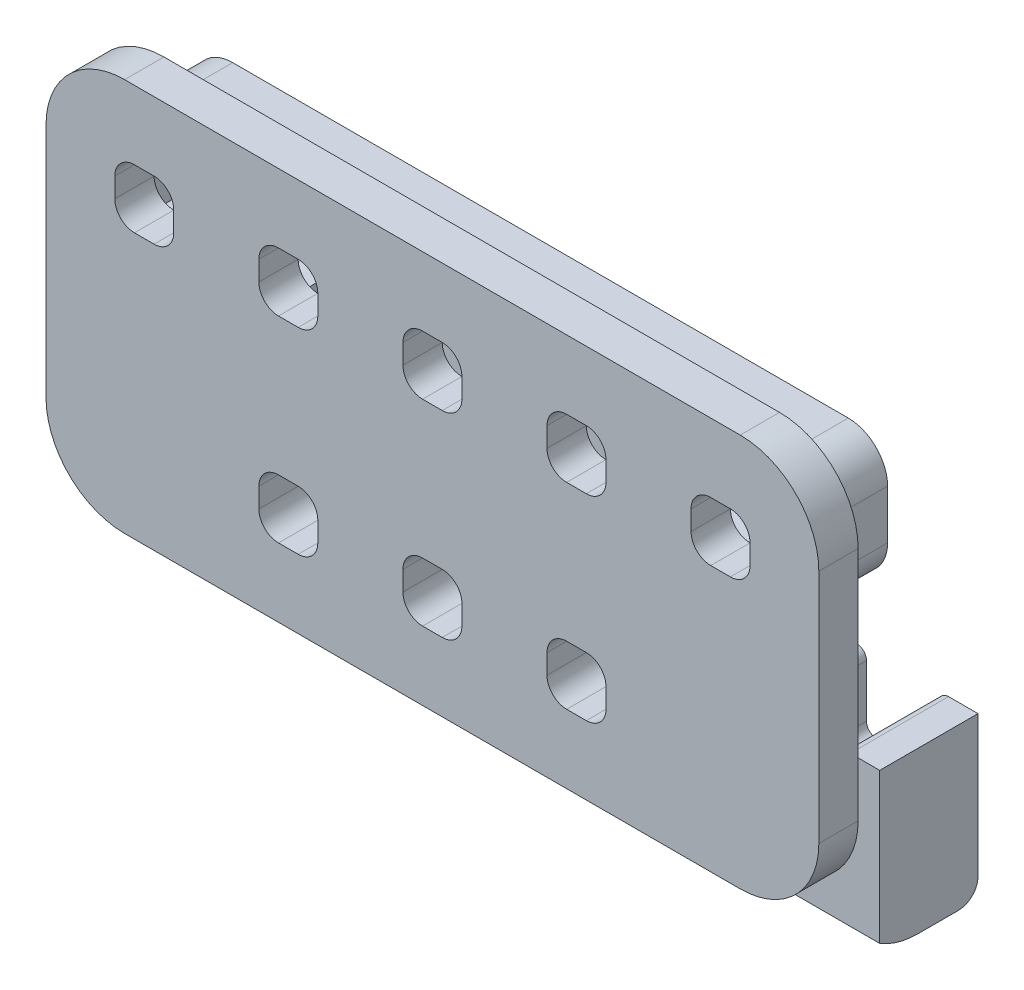
SolidWorks part; units mm, degrees
ref_plane "Front Plane" through (0, 0, 0) normal (0, 0, 1) x (1, 0, 0)
ref_plane "Top Plane" through (0, 0, 0) normal (0, 1, 0) x (1, 0, 0)
ref_plane "Right Plane" through (0, 0, 0) normal (1, 0, 0) x (0, 0, -1)
sketch "Sketch1" plane through (0, 0, 0) normal (0, 0, 1) x (1, 0, 0)
  line L0 (-3.675, 0) -> (-3.675, 7.35) construction
  line L1 (0, 0) -> (-7.35, 0)
  line L2 (0, 0) -> (0, 7.35)
  line L3 (0, 7.35) -> (-7.35, 7.35) construction
  line L4 (-7.35, 0) -> (-7.35, 7.35)
  line L5 (0, 7.35) -> (4, 7.35)
  line L6 (4, 7.35) -> (4, -9)
  line L7 (4, -9) -> (-11.35, -9)
  line L8 (-3.675, -9) -> (-3.675, 0) construction
  line L9 (-11.35, 7.35) -> (-11.35, -9)
  line L10 (-7.35, 7.35) -> (-11.35, 7.35)
  arc A0 (-11.35, -2.7355) -> (4, -2.7355) centre (-3.675, 3.675) ccw
  arc A1 (4, -2.7355) -> (-11.35, -2.7355) centre (-3.675, 3.675) ccw construction
  arc A2 (4, -6.4121) -> (-11.35, -6.4121) centre (-3.675, 3.675) ccw
  arc A3 (-3.675, -9) -> (4, -6.4121) centre (-3.675, 3.675) ccw construction
  arc A4 (-11.35, -6.4121) -> (-3.675, -9) centre (-3.675, 3.675) ccw construction
  point P14 (0, 0)
  dimension "D2" = 20
  dimension "D1" = 7.35
  dimension "D3" = 9
  dimension "D4" = 4
extrude "Boss-Extrude1" add sketch "Sketch1" along normal blind 10 contours L7 L9 L10 L4 L1 L2 L5 L6
sketch "Sketch2" plane through (4, 0, 0) normal (1, 0, 0) x (0, 0, -1)
  line L0 (0, 7.35) -> (0, -9) construction
  line L1 (-10, -9) -> (0, -9)
  line L2 (-10, -9) -> (-10, -3)
  line L3 (-10, -3) -> (0, -3)
  line L4 (0, -9) -> (0, -3)
  dimension "D1" = 6
extrude "Boss-Extrude2" add sketch "Sketch2" along normal blind 23.975
sketch "Sketch3" plane through (0, 0, 10) normal (0, 0, 1) x (1, 0, 0)
  line L0 (27.975, -3) -> (27.975, -9) construction
  line L1 (4, -9) -> (27.975, -9)
  line L2 (4, -9) -> (4, 5.85)
  line L3 (4, 5.85) -> (27.975, 5.85)
  line L4 (27.975, -9) -> (27.975, 5.85)
  line L5 (0, 7.35) -> (4, 7.35) construction
  line L6 (-3.675, 0) -> (-3.675, 7.35) construction
  circle A0 centre (-3.675, 3.675) radius 10
  line M3 (4, -3) -> (4, 7.35)
  line M10 (-11.35, -9) -> (27.975, -9)
  line M11 (27.975, -9) -> (27.975, -3)
  line M12 (27.975, -3) -> (4, -3)
  dimension "D2" = 20
  dimension "D1" = 1.5
extrude "Boss-Extrude4" add sketch "Sketch3" along normal blind 2.2 and the other way blind 4 contours A0 L4 L3 M3 M12 | L2 M10 M11 M12 region at (15.9875, -6, 10) region at (16.828, 1.3529, 10)
extrude "Boss-Extrude5" add sketch "Sketch3<3>" against normal blind 4 contours L2 A0 L3 region at (4.9995, 2.3673, 10)
sketch "Sketch3<3>" plane through (0, 0, 10) normal (0, 0, 1) x (1, 0, 0) same geometry as "Sketch3"
mirror "Mirror1" about plane through (27.975, 0, 0) normal (-1, 0, 0) of bodies 104
sketch "Sketch5" plane through (0, 0, 12.2) normal (0, 0, 1) x (1, 0, 0)
  line L0 (-11.35, 7.35) -> (-11.35, -9) construction
  line L1 (-11.35, -4) -> (67.3, -4)
  line L2 (-11.35, -4) -> (-11.35, 36)
  line L3 (-11.35, 36) -> (67.3, 36)
  line L4 (67.3, -4) -> (67.3, 36)
  line L5 (67.3, 7.35) -> (67.3, -9) construction
  line L6 (4, -9) -> (51.95, -9) construction
  dimension "D1" = 5
  dimension "D2" = 40
extrude "Boss-Extrude6" add sketch "Sketch5" along normal blind 4
sketch "Sketch6" plane through (67.3, 0, 0) normal (1, 0, 0) x (0, 0, -1)
  line L0 (-6.1, -1.5) -> (-6.1, -9) construction
  line L1 (0, -5.8635) -> (0, -9)
  line L2 (0, -9) -> (-12.2, -9)
  line L3 (-12.2, -9) -> (-12.2, -5.8635)
  line L4 (-12.2, -9) -> (-12.2, -4) construction
  arc A0 (-12.2, -5.8635) -> (0, -5.8635) centre (-6.1, -1.5) ccw
  line M7 (-10, 7.35) -> (-10, -9)
  line M8 (-10, -9) -> (0, -9)
  dimension "D1" = 15
extrude "Cut-Extrude1" cut sketch "Sketch6" against normal through all contours A0 L3 L2 M7 | A0 M7 M8 region at (67.3, -8.6764, 9.0398) region at (67.3, -7.9254, 11.2866)
fillet "Fillet1" radius 2 1 edges at (27.975, -9, 0)
sketch "Sketch7" plane through (0, 0, 16.2) normal (0, 0, 1) x (1, 0, 0)
  line L0 (-11.35, 36) -> (-11.35, -4) construction
  line L1 (-4.35, 29) -> (1.65, 29)
  line L2 (-4.35, 29) -> (-4.35, 23)
  line L3 (-4.35, 23) -> (1.65, 23)
  line L4 (1.65, 29) -> (1.65, 23)
  line L5 (67.3, 36) -> (-11.35, 36) construction
  line L6 (10.3125, 29) -> (10.3125, 23)
  line L7 (10.3125, 29) -> (16.3125, 29)
  line L8 (16.3125, 29) -> (16.3125, 23)
  line L9 (10.3125, 23) -> (16.3125, 23)
  line L10 (24.975, 29) -> (24.975, 23)
  line L11 (24.975, 29) -> (30.975, 29)
  line L12 (30.975, 29) -> (30.975, 23)
  line L13 (24.975, 23) -> (30.975, 23)
  line L14 (39.6375, 29) -> (39.6375, 23)
  line L15 (39.6375, 29) -> (45.6375, 29)
  line L16 (45.6375, 29) -> (45.6375, 23)
  line L17 (39.6375, 23) -> (45.6375, 23)
  line L18 (10.3125, 9) -> (10.3125, 3)
  line L19 (10.3125, 9) -> (16.3125, 9)
  line L20 (16.3125, 9) -> (16.3125, 3)
  line L21 (10.3125, 3) -> (16.3125, 3)
  line L22 (24.975, 9) -> (24.975, 3)
  line L23 (24.975, 9) -> (30.975, 9)
  line L24 (30.975, 9) -> (30.975, 3)
  line L25 (24.975, 3) -> (30.975, 3)
  line L26 (39.6375, 9) -> (39.6375, 3)
  line L27 (39.6375, 9) -> (45.6375, 9)
  line L28 (45.6375, 9) -> (45.6375, 3)
  line L29 (39.6375, 3) -> (45.6375, 3)
  line L30 (-4.35, 9) -> (-4.35, 3) [skipped]
  line L31 (-4.35, 9) -> (1.65, 9) [skipped]
  line L32 (1.65, 9) -> (1.65, 3) [skipped]
  line L33 (-4.35, 3) -> (1.65, 3) [skipped]
  line L35 (13.3125, 9) -> (13.3125, 23) construction
  line L36 (54.3, 29) -> (54.3, 23)
  line L37 (54.3, 29) -> (60.3, 29)
  line L38 (60.3, 29) -> (60.3, 23)
  line L39 (54.3, 23) -> (60.3, 23)
  line L44 (67.3, -4) -> (67.3, 36) construction
  line L45 (54.3, 3) -> (60.3, 3) [skipped]
  line L46 (54.3, 9) -> (54.3, 3) [skipped]
  line L47 (54.3, 9) -> (60.3, 9) [skipped]
  line L48 (60.3, 9) -> (60.3, 3) [skipped]
  dimension "D1" = 6
  dimension "D2" = 7
  dimension "D3" = 7
  dimension "D6" = 14
  dimension "D7" = 7
  dimension "D5" = 5
  dimension "D4" = 2
extrude "Cut-Extrude2" cut sketch "Sketch7" against normal blind 45
fillet "Fillet2" radius 2 32 edges at (10.3125, 3, 11.1) (16.3125, 3, 11.1) (16.3125, 9, 14.2) (10.3125, 9, 14.2) (39.6375, 23, 14.2) (45.6375, 23, 14.2) (45.6375, 29, 14.2) (39.6375, 29, 14.2) (24.975, 23, 14.2) (30.975, 23, 14.2) (30.975, 29, 14.2) (24.975, 29, 14.2) (10.3125, 23, 14.2) (16.3125, 23, 14.2) (16.3125, 29, 14.2) (10.3125, 29, 14.2) (24.975, 3, 11.1) (30.975, 3, 11.1) (30.975, 9, 14.2) (24.975, 9, 14.2) (1.65, 23, 14.2) (1.65, 29, 14.2) (-4.35, 29, 14.2) (-4.35, 23, 14.2) (39.6375, 3, 11.1) (45.6375, 3, 11.1) (45.6375, 9, 14.2) (39.6375, 9, 14.2) (54.3, 23, 14.2) (60.3, 23, 14.2) (60.3, 29, 14.2) (54.3, 29, 14.2)
fillet "Fillet3" radius 8 4 edges at (-11.35, 36, 14.2) (67.3, -4, 14.2) (-11.35, -4, 14.2) (67.3, 36, 14.2)
sketch "Sketch8" plane through (0, 0, 12.2) normal (0, 0, -1) x (-1, 0, 0)
  line L0 (-41.6375, 29) -> (-43.6375, 29) construction
  line L1 (-63.3, 32) -> (7.35, 32)
  line L2 (-63.3, 32) -> (-63.3, 19)
  line L3 (-63.3, 19) -> (-48.6375, 19)
  line L4 (7.35, 32) -> (7.35, 19)
  line L6 (4.35, 25) -> (4.35, 27) construction
  line L7 (-7.3125, 19) -> (-7.3125, 0)
  line L8 (-7.3125, 0) -> (-48.6375, 0)
  line L9 (-48.6375, 0) -> (-48.6375, 19)
  line L10 (-27.975, 0) -> (-27.975, 19) construction
  line L11 (-10.3125, 5.85) -> (-10.3125, 7) construction
  line L12 (-14.3125, 23) -> (-12.3125, 23) construction
  line L13 (-48.6375, 19) -> (-27.975, 19) construction
  line L14 (-7.3125, 19) -> (7.35, 19)
  line L15 (-27.975, 19) -> (-7.3125, 19) construction
  line L17 (-60.3, 27) -> (-60.3, 25) construction
  point P17 (-29.546, 18.0876)
  dimension "D1" = 3
  dimension "D2" = 3
  dimension "D3" = 3
  dimension "D4" = 3
  dimension "D5" = 4
  dimension "D6" = 3
extrude "Boss-Extrude7" add sketch "Sketch8" along normal blind 3 from offset 4
extrude "Extrude-Thin1" add sketch "Sketch8<2>" along normal up to surface (7 mm away) thin up to face at (27.975, 17.5, 5.2) thin type one direction reverse wall 2
sketch "Sketch8<2>" plane through (0, 0, 12.2) normal (0, 0, -1) x (-1, 0, 0) same geometry as "Sketch8"
fillet "Fillet4" radius 4 8 edges at (63.3, 32, 8.7) (-7.35, 32, 8.7) (-7.35, 19, 8.7) (7.3125, 19, 8.7) (7.3125, 0, 5.6) (48.6375, 0, 5.6) (48.6375, 19, 8.7) (63.3, 19, 8.7)
fillet "Fillet5" radius 1 8 edges at (63.3, 7.35, 5) (55.95, 7.35, 5) (-7.35, 7.35, 5) (0, 7.35, 5) (-7.35, 0, 5) (0, 0, 5) (63.3, 0, 5) (55.95, 0, 5)
